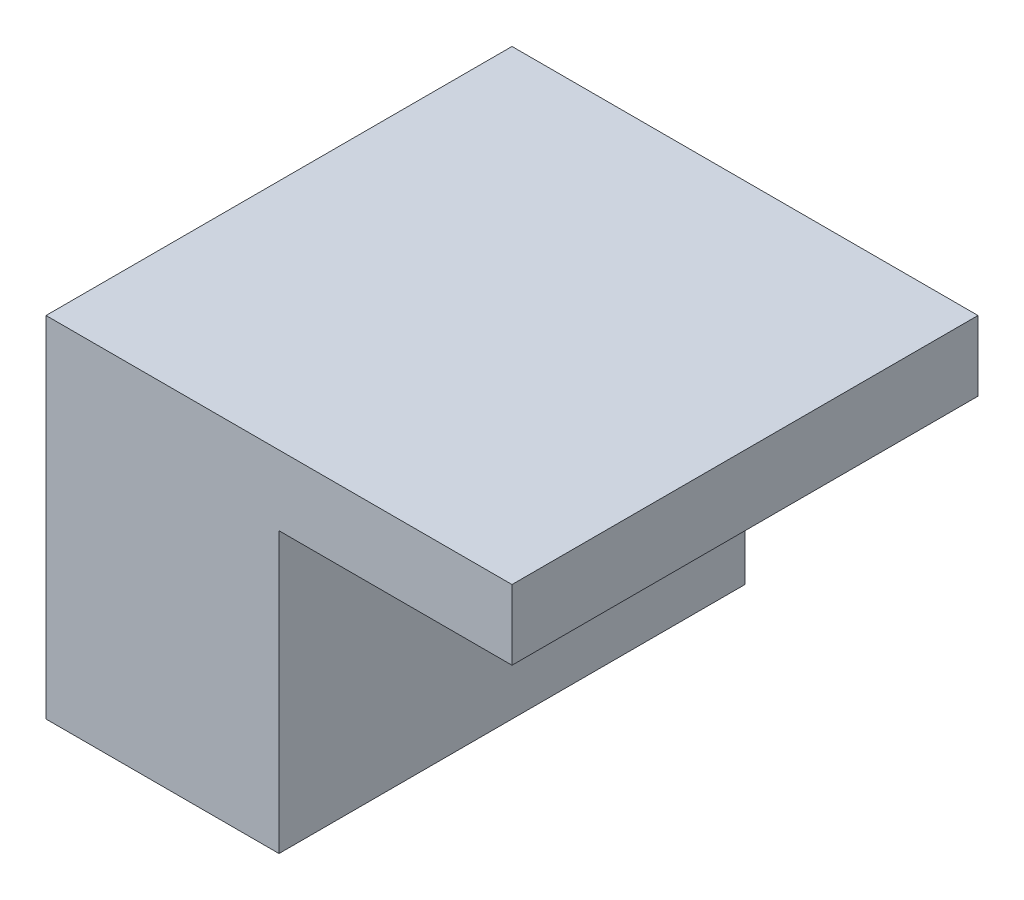
SolidWorks part; units mm, degrees
ref_plane "정면" through (0, 0, 0) normal (0, 0, 1) x (1, 0, 0)
ref_plane "윗면" through (0, 0, 0) normal (0, 1, 0) x (1, 0, 0)
ref_plane "우측면" through (0, 0, 0) normal (1, 0, 0) x (0, 0, -1)
sketch "스케치1" plane through (0, 0, 0) normal (0, 1, 0) x (1, 0, 0)
  line L0 (0, 100) -> (0, -100)
  line L1 (-100, -100) -> (100, -100)
  line L2 (-100, -100) -> (-100, 100)
  line L3 (-100, 100) -> (100, 100)
  line L4 (100, -100) -> (100, 100)
  line L5 (-100, -100) -> (100, 100) construction
  line L6 (-100, 100) -> (100, -100) construction
  line L7 (-90, 90) -> (-90, -90)
  line L8 (-90, -90) -> (-10, -90)
  line L9 (-10, -90) -> (-10, 90)
  line L10 (-10, 90) -> (-90, 90)
  point P0 (0, 0)
  point P10 (0, 0)
  point P13 (0, 0)
  dimension "D1" = 200
  dimension "D2" = 200
  dimension "D3" = 80
  dimension "D4" = 180
  dimension "D5" = 10
  dimension "D6" = 10
extrude "보스-돌출1" add sketch "스케치1" along normal blind 150 contours L3 L2 L1 L0 region at (-2.2361, 0, 0)
extrude "보스-돌출2" add sketch "스케치1<3>" against normal blind 30 from surface contours L1 L4 L3 L0 region at (50, 0, 0) starting at face at (-50, 150, 0)
sketch "스케치1<3>" plane through (0, 0, 0) normal (0, 1, 0) x (1, 0, 0) same geometry as "스케치1"
extrude "보스-돌출3" add sketch "스케치1<4>" along normal blind 30 contours L9 L10 L7 L8 region at (-50, 0, 0)
sketch "스케치1<4>" plane through (0, 0, 0) normal (0, 1, 0) x (1, 0, 0) same geometry as "스케치1"
extrude "보스-돌출4" add sketch "스케치1<5>" against normal blind 30 from surface contours L9 L10 L7 L8 region at (-50, 0, 0) starting at face at (-50, 150, 0)
sketch "스케치1<5>" plane through (0, 0, 0) normal (0, 1, 0) x (1, 0, 0) same geometry as "스케치1"
sketch "스케치5" plane through (0, 0, 0) normal (1, 0, 0) x (0, 0, -1)
  line L0 (0, 0) -> (0, 50) construction
  dimension "D1" = 50
